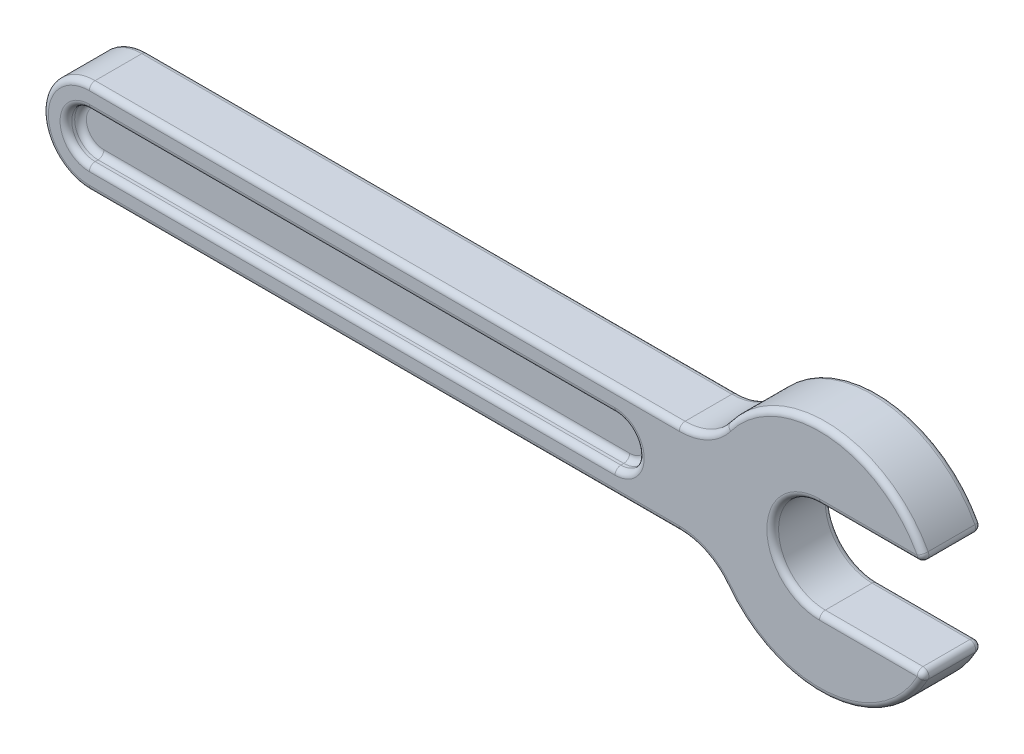
SolidWorks part; units mm, degrees
ref_plane "Front Plane" through (0, 0, 0) normal (0, 0, 1) x (1, 0, 0)
ref_plane "Top Plane" through (0, 0, 0) normal (0, 1, 0) x (1, 0, 0)
ref_plane "Right Plane" through (0, 0, 0) normal (1, 0, 0) x (0, 0, -1)
sketch "Sketch1" plane through (0, 0, 0) normal (0, 0, 1) x (1, 0, 0)
  line L0 (0, 0) -> (41310.0533, 0) construction
  line L1 (0, 0) -> (0, 41310.0533) construction
  line L2 (36.6606, 16) -> (0, 16)
  line L3 (0, -16) -> (36.6606, -16)
  line L4 (-48, 16) -> (-250, 16)
  line L5 (-48, -16) -> (-250, -16)
  line L6 (-250, 0) -> (-70, 0) construction
  line L7 (-250, 8) -> (-70, 8)
  line L8 (-250, -8) -> (-70, -8)
  arc A0 (36.6606, 16) -> (-32, 24) centre (0, 0) ccw
  arc A1 (0, 16) -> (0, -16) centre (0, 0) ccw
  circle A2 centre (0, 27.5) radius 5
  circle A4 centre (27.5, 0) radius 5 [skipped]
  circle A5 centre (0, -27.5) radius 5
  circle A6 centre (-27.5, 0) radius 5
  arc A7 (-250, 16) -> (-250, -16) centre (-250, 0) ccw
  arc A8 (-250, 8) -> (-250, -8) centre (-250, 0) ccw
  arc A9 (-70, -8) -> (-70, 8) centre (-70, 0) ccw
  arc A10 (-32, -24) -> (36.6606, -16) centre (0, 0) ccw
  arc A11 (-32, -24) -> (-48, -16) centre (-48, -36) ccw
  arc A12 (-32, 24) -> (-48, 16) centre (-48, 36) cw
  point P10 (-160, 0)
  point P21 (0, 0)
  point P30 (0, 0)
  dimension "D1" = 80
  dimension "D2" = 10
  dimension "D3" = 4
  dimension "D5" = 16
  dimension "D8" = 8
  dimension "D9" = 20
  dimension "D4" = 55
  dimension "D6" = 250
  dimension "D7" = 180
extrude "Boss-Extrude5" add sketch "Sketch1" along normal mid plane 20 contours L3 A10 A11 L5 A7 L4 A12 A0 L2 A1 | L8 A9 L7 A8
extrude "Boss-Extrude6" add sketch "Sketch1<8>" along normal mid plane 10 contours L8 A9 L7 A8 region at (-160, 0, 0)
sketch "Sketch1<8>" plane through (0, 0, 0) normal (0, 0, 1) x (1, 0, 0) same geometry as "Sketch1"
fillet "Fillet1" radius 2 38 edges at (36.6606, 16, 0) (36.6606, -16, 0) (18.3303, 16, 10) (4.6293, 39.7312, 10) (-39.0557, 18.1115, 10) (-149, 16, 10) (-266, 0, 10) (-149, -16, 10) (-39.0557, -18.1115, 10) (4.6293, -39.7312, 10) (18.3303, -16, 10) (-16, 0, 10) (18.3303, 16, -10) (4.6293, 39.7312, -10) (-39.0557, 18.1115, -10) (-149, 16, -10) (-266, 0, -10) (-149, -16, -10) (-39.0557, -18.1115, -10) (4.6293, -39.7312, -10) (18.3303, -16, -10) (-16, 0, -10) (-160, 8, 10) (-62, 0, 10) (-160, -8, 10) (-258, 0, 10) (-160, 8, -10) (-62, 0, -10) (-160, -8, -10) (-258, 0, -10) (-258, 0, 5) (-160, 8, 5) (-62, 0, 5) (-160, -8, 5) (-258, 0, -5) (-160, 8, -5) (-62, 0, -5) (-160, -8, -5)
